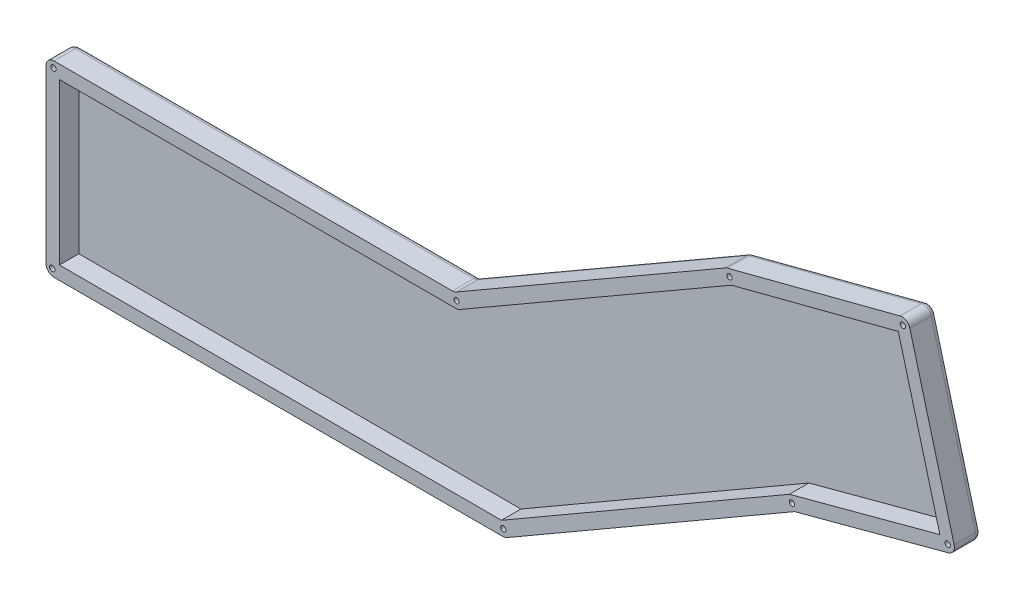
SolidWorks part; units mm, degrees
ref_plane "Plan de face" through (0, 0, 0) normal (0, 0, 1) x (1, 0, 0)
ref_plane "Plan de dessus" through (0, 0, 0) normal (0, 1, 0) x (1, 0, 0)
ref_plane "Plan de droite" through (0, 0, 0) normal (1, 0, 0) x (0, 0, -1)
sketch "Model" plane through (0, 0, 0) normal (0, 0, 1) x (1, 0, 0)
  line L0 (152.8114, 25.9717) -> (138.2826, 80.2215) construction
  line L1 (98.1506, 11.3316) -> (152.8114, 25.9717) construction
  line L2 (-9.3986, -50.8585) -> (98.1506, 11.3316) construction
  line L3 (-172.3739, -50.8585) -> (-9.3986, -50.8585) construction
  line L4 (-24.5886, 5.3017) -> (-172.3739, 5.2915) construction
  line L5 (138.2826, 80.2215) -> (78.0109, 64.5416) construction
  line L6 (-151.6088, 5.3124) -> (-151.6088, 5.2929)
  line L7 (-24.5886, 5.3017) -> (78.0109, 64.5416) construction
  line L8 (-172.3739, 5.2915) -> (-172.3739, -50.6876) construction
  line L9 (-172.3739, -50.6876) -> (-172.3739, -50.8585) construction
  line L10 (-25.1245, 7.3016) -> (-174.3739, 7.2914)
  line L11 (-174.3739, 7.2914) -> (-174.3739, -50.6876)
  line L12 (-174.3739, -50.6876) -> (-174.3739, -52.8585)
  line L13 (-174.3739, -52.8585) -> (-8.862, -52.8585)
  line L14 (-8.862, -52.8585) -> (98.9231, 9.4681)
  line L15 (98.9231, 9.4681) -> (155.2607, 24.5572)
  line L16 (155.2607, 24.5572) -> (139.7008, 82.657)
  line L17 (139.7008, 82.657) -> (77.2454, 66.409)
  line L18 (-25.1245, 7.3016) -> (77.2454, 66.409)
  line L19 (-26.4645, 12.3015) -> (-179.3739, 12.291)
  line L20 (-179.3739, 12.291) -> (-179.3739, -50.6876)
  line L21 (-179.3739, -50.6876) -> (-179.3739, -57.8585)
  line L22 (-179.3739, -57.8585) -> (-7.5204, -57.8585)
  line L23 (-7.5204, -57.8585) -> (100.8545, 4.8091)
  line L24 (100.8545, 4.8091) -> (161.3839, 21.021)
  line L25 (161.3839, 21.021) -> (143.2464, 88.7459)
  line L26 (143.2464, 88.7459) -> (75.3314, 71.0775)
  line L27 (-26.4645, 12.3015) -> (75.3314, 71.0775)
  circle A0 centre (80.6856, 58.4893) radius 1
  circle A1 centre (92.8776, 28.0855) radius 1
  circle A2 centre (-29.7028, -2.6485) radius 1
  circle A3 centre (-10.6528, -46.4381) radius 1
  circle A4 centre (-114.2594, -13.4181) radius 1
  circle A5 centre (-114.0308, -32.4935) radius 1
  dimension "D1" = 2
  dimension "D2" = 5
extrude "Boss.-Extru.1" add sketch "Model" along normal blind 10 contours L27 L19 L20 L21 L22 L23 L24 L25 L26 L10 L18 L17 L16 L15 L14 L13 L12 L11 region at (26.2883, 38.477, 0)
fillet "Congé1" radius 3 8 edges at (-26.4645, 12.3015, 5) (75.3314, 71.0775, 5) (143.2464, 88.7459, 5) (161.3839, 21.021, 5) (100.8545, 4.8091, 5) (-7.5204, -57.8585, 5) (-179.3739, -57.8585, 5) (-179.3739, 12.291, 5)
sketch "Esquisse1" plane through (0, 0, 0) normal (0, 0, 1) x (1, 0, 0)
  line L0 (-25.1245, 7.3016) -> (-174.3739, 7.2914) construction
  line L1 (-25.1245, 7.3016) -> (77.2454, 66.409) construction
  line L2 (139.7008, 82.657) -> (77.2454, 66.409) construction
  line L3 (155.2607, 24.5572) -> (139.7008, 82.657) construction
  line L4 (98.9231, 9.4681) -> (155.2607, 24.5572) construction
  line L5 (-8.862, -52.8585) -> (98.9231, 9.4681) construction
  line L6 (-174.3739, -52.8585) -> (-8.862, -52.8585) construction
  line L7 (-174.3739, -50.6876) -> (-174.3739, -52.8585) construction
  line L8 (-174.3739, 7.2914) -> (-174.3739, -50.6876) construction
  line L9 (-25.1245, 7.3016) -> (-174.3739, 7.2914)
  line L10 (-25.1245, 7.3016) -> (77.2454, 66.409)
  line L11 (139.7008, 82.657) -> (77.2454, 66.409)
  line L12 (155.2607, 24.5572) -> (139.7008, 82.657)
  line L13 (98.9231, 9.4681) -> (155.2607, 24.5572)
  line L14 (-8.862, -52.8585) -> (98.9231, 9.4681)
  line L15 (-174.3739, -52.8585) -> (-8.862, -52.8585)
  line L16 (-174.3739, -50.6876) -> (-174.3739, -52.8585)
  line L17 (-174.3739, 7.2914) -> (-174.3739, -50.6876)
  point P27 (0, 0)
extrude "Boss.-Extru.2" add sketch "Esquisse1" along normal blind 2.7
sketch "Esquisse3" plane through (0, 0, 0) normal (0, 0, 1) x (1, 0, 0)
  circle A0 centre (158.2016, 22.9581) radius 1
  circle A1 centre (141.3885, 85.5343) radius 1
  circle A2 centre (76.5002, 68.7766) radius 1
  circle A3 centre (99.8904, 7.0714) radius 1
  circle A4 centre (-8.1724, -55.2759) radius 1
  circle A5 centre (-25.6914, 9.9201) radius 1
  circle A6 centre (-176.5621, 9.9201) radius 1
  circle A7 centre (-177.0296, -55.2759) radius 1
sketch "Esquisse2" plane through (0, 0, 0) normal (0, 0, -1) x (-1, 0, 0)
  circle A0 centre (-80.6856, 58.4893) radius 1 construction
  circle A1 centre (-92.8776, 28.0855) radius 1 construction
  circle A2 centre (29.7028, -2.6485) radius 1 construction
  circle A3 centre (10.6528, -46.4381) radius 1 construction
  circle A4 centre (114.2594, -13.4181) radius 1 construction
  circle A5 centre (114.0308, -32.4935) radius 1 construction
  circle A6 centre (-80.6856, 58.4893) radius 1
  circle A7 centre (-92.8776, 28.0855) radius 1
  circle A8 centre (29.7028, -2.6485) radius 1
  circle A9 centre (10.6528, -46.4381) radius 1
  circle A10 centre (114.2594, -13.4181) radius 1
  circle A11 centre (114.0308, -32.4935) radius 1
  circle A12 centre (-80.6856, 58.4893) radius 2
  circle A13 centre (-92.8776, 28.0855) radius 2
  circle A14 centre (29.7028, -2.6485) radius 2
  circle A15 centre (10.6528, -46.4381) radius 2
  circle A16 centre (114.2594, -13.4181) radius 2
  circle A17 centre (114.0308, -32.4935) radius 2
  point P30 (114.0308, -32.4935)
  dimension "D1" = 1
fillet "Congé2" radius 2 16 edges at (100.8645, 4.785, 0) (46.844, -26.4224, 0) (-7.5479, -57.756, 0) (-92.3496, -57.8585, 0) (-178.4952, -56.9798, 0) (-179.3739, -22.7836, 0) (-178.4953, 11.4125, 0) (-101.8212, 12.2964, 0) (-26.4919, 12.4038, 0) (24.6056, 41.7889, 0) (75.3418, 71.0522, 0) (108.0441, 79.5878, 0) (142.6286, 87.6851, 0) (152.3124, 54.8937, 0) (160.3079, 21.6424, 0) (129.8616, 12.5782, 0)
extrude "Enlèv. mat.-Extru.1" cut sketch "Esquisse3" along normal blind 20
sketch "Esquisse4" plane through (0, 0, 0) normal (0, 0, -1) x (-1, 0, 0)
  circle A0 centre (177.0296, -55.2759) radius 2
  circle A1 centre (176.5621, 9.9201) radius 2
  circle A2 centre (25.6914, 9.9201) radius 2
  circle A3 centre (-76.5002, 68.7766) radius 2
  circle A4 centre (-141.3885, 85.5343) radius 2
  circle A5 centre (-158.2016, 22.9581) radius 2
  circle A6 centre (-99.8904, 7.0714) radius 2
  circle A7 centre (8.1724, -55.2759) radius 2
extrude "Enlèv. mat.-Extru.2" cut sketch "Esquisse4" against normal blind 2
